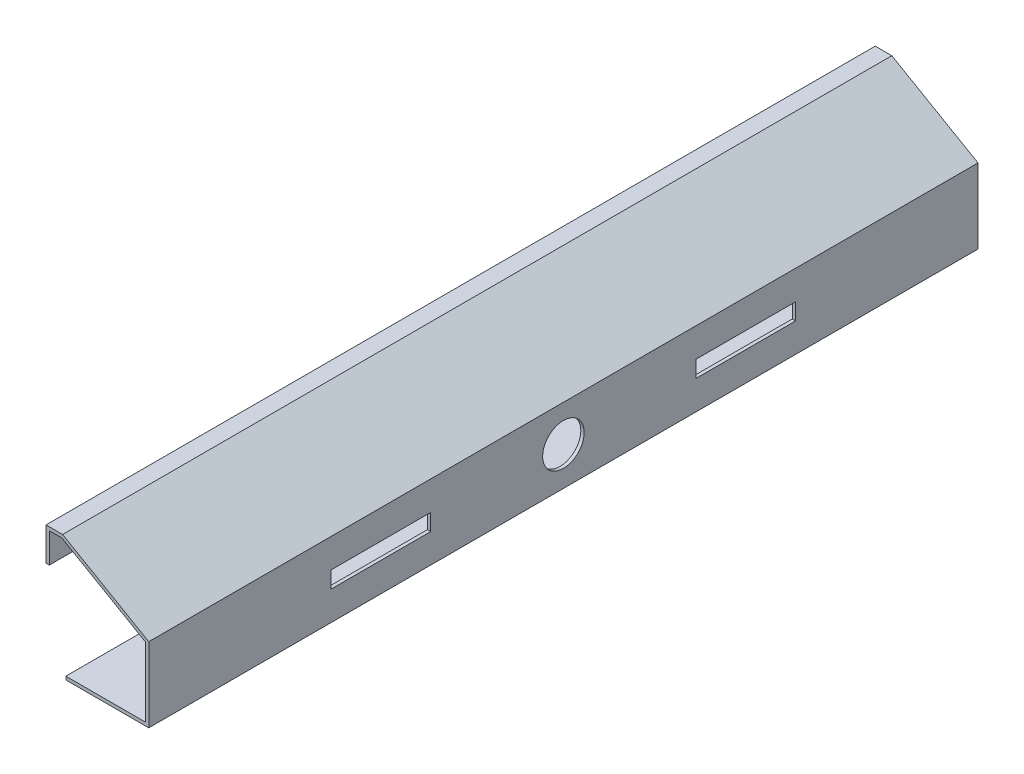
SolidWorks part; units mm, degrees
material "Wrought Stainless Steel"
ref_plane "Front Plane" through (0, 0, 0) normal (0, 0, 1) x (1, 0, 0)
ref_plane "Top Plane" through (0, 0, 0) normal (0, 1, 0) x (1, 0, 0)
ref_plane "Right Plane" through (0, 0, 0) normal (1, 0, 0) x (0, 0, -1)
sketch "Sketch1" plane through (0, 0, 0) normal (0, 0, 1) x (1, 0, 0)
  line L0 (0, 0) -> (-51.9615, 30)
  line L1 (-51.9615, 30) -> (-61.9615, 30)
  line L2 (0, 0) -> (0, -45)
  line L3 (0, -45) -> (-50, -45)
  line L4 (-2, -43) -> (-50, -43)
  line L5 (-2, -1.1547) -> (-2, -43)
  line L6 (-2, -1.1547) -> (-52.4974, 28)
  line L7 (-52.4974, 28) -> (-61.9615, 28)
  line L8 (-61.9615, 30) -> (-61.9615, 28)
  line L9 (-50, -43) -> (-50, -45)
  dimension "D1" = 45
  dimension "D2" = 60
  dimension "D3" = 10
  dimension "D4" = 120
  dimension "D5" = 50
  dimension "D6" = 2
extrude "Boss-Extrude1" add sketch "Sketch1" along normal blind 500
sketch "Sketch2" plane through (0, 0, 0) normal (1, 0, 0) x (0, 0, -1)
  line L0 (-500, -45) -> (0, -45) construction
  line L1 (0, -45) -> (0, 0) construction
  circle A0 centre (-250, -22) radius 12.5
  dimension "D1" = 25
  dimension "D2" = 23
  dimension "D3" = 250
extrude "Cut-Extrude1" cut sketch "Sketch2" against normal through all
sketch "Sketch3" plane through (0, 0, 0) normal (1, 0, 0) x (0, 0, -1)
  line L0 (-250, 0) -> (-250, -45) construction
  line L1 (-500, 0) -> (0, 0) construction
  line L2 (-500, -45) -> (0, -45) construction
  line L3 (-110, -17.5) -> (-170, -17.5)
  line L4 (-390, -27.5) -> (-330, -27.5)
  line L5 (-390, -27.5) -> (-390, -17.5)
  line L6 (-390, -17.5) -> (-330, -17.5)
  line L7 (-330, -27.5) -> (-330, -17.5)
  line L8 (-390, -27.5) -> (-330, -17.5) construction
  line L9 (-390, -17.5) -> (-330, -27.5) construction
  line L10 (-170, -27.5) -> (-170, -17.5)
  line L11 (-110, -27.5) -> (-170, -27.5)
  line L12 (-110, -27.5) -> (-110, -17.5)
  point P6 (-360, -22.5)
  dimension "D1" = 60
  dimension "D2" = 10
  dimension "D3" = 22.5
  dimension "D4" = 80
extrude "Cut-Extrude2" cut sketch "Sketch3" against normal blind 2
sketch "Sketch4" plane through (-61.9615, 0, 0) normal (-1, 0, 0) x (0, 0, 1)
  line L0 (500, 30) -> (0, 30) construction
  line L1 (0, 10) -> (500, 10)
  line L2 (0, 10) -> (0, 30)
  line L3 (0, 30) -> (500, 30)
  line L4 (500, 10) -> (500, 30)
  line L5 (0, 10) -> (500, 30) construction
  line L6 (0, 30) -> (500, 10) construction
  line L7 (0, 28) -> (0, -1.1547) construction
  point P0 (250, 20)
  dimension "D1" = 500
  dimension "D2" = 20
  dimension "D3" = 10
  dimension "D4" = 0
extrude "Boss-Extrude2" add sketch "Sketch4" against normal blind 2
